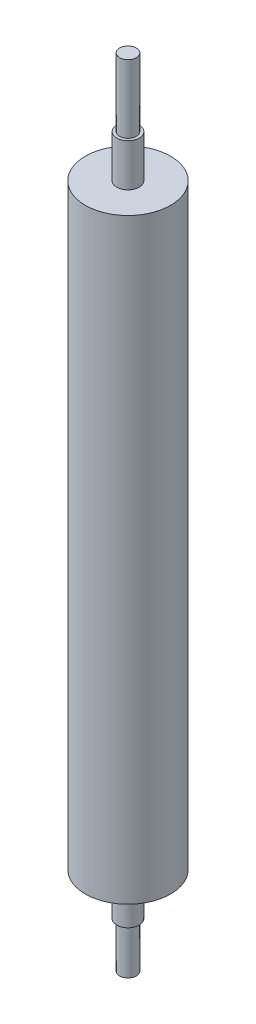
SolidWorks part; units mm, degrees
material "Stainless Steel (ferritic)"
ref_plane "Front Plane" through (0, 0, 0) normal (0, 0, 1) x (1, 0, 0)
ref_plane "Top Plane" through (0, 0, 0) normal (0, 1, 0) x (1, 0, 0)
ref_plane "Right Plane" through (0, 0, 0) normal (1, 0, 0) x (0, 0, -1)
sketch "Sketch1" plane through (0, 0, 0) normal (0, 1, 0) x (1, 0, 0)
  circle A0 centre (0, 0) radius 3.95
  circle A1 centre (0, 0) radius 3.45
  circle A2 centre (0, 0) radius 2.95
  circle A3 centre (0, 0) radius 15
  dimension "D1" = 7.9
  dimension "D2" = 6.9
  dimension "D3" = 5.9
  dimension "D4" = 30
extrude "Boss-Extrude8" add sketch "Sketch1" along normal blind 210 contours A3
extrude "Boss-Extrude9" add sketch "Sketch1<9>" against normal blind 15 contours A0
sketch "Sketch1<9>" plane through (0, 0, 0) normal (0, 1, 0) x (1, 0, 0) same geometry as "Sketch1"
extrude "Boss-Extrude10" add sketch "Sketch1<10>" against normal blind 16 from surface contours A2 region at (0, 0, 0) starting at face at (0, -15, 3.95)
sketch "Sketch1<10>" plane through (0, 0, 0) normal (0, 1, 0) x (1, 0, 0) same geometry as "Sketch1"
extrude "Boss-Extrude11" add sketch "Sketch1<11>" along normal blind 15 from surface contours A0 starting at face at (0, 210, 15)
sketch "Sketch1<11>" plane through (0, 0, 0) normal (0, 1, 0) x (1, 0, 0) same geometry as "Sketch1"
sketch "Sketch2" plane through (0, 225, 0) normal (0, 1, 0) x (1, 0, 0)
  circle A0 centre (0, 0) radius 2.95
  circle A1 centre (0, 0) radius 3.45
extrude "Boss-Extrude12" add sketch "Sketch2" along normal blind 24 contours A0 region at (0, 225, 0)
